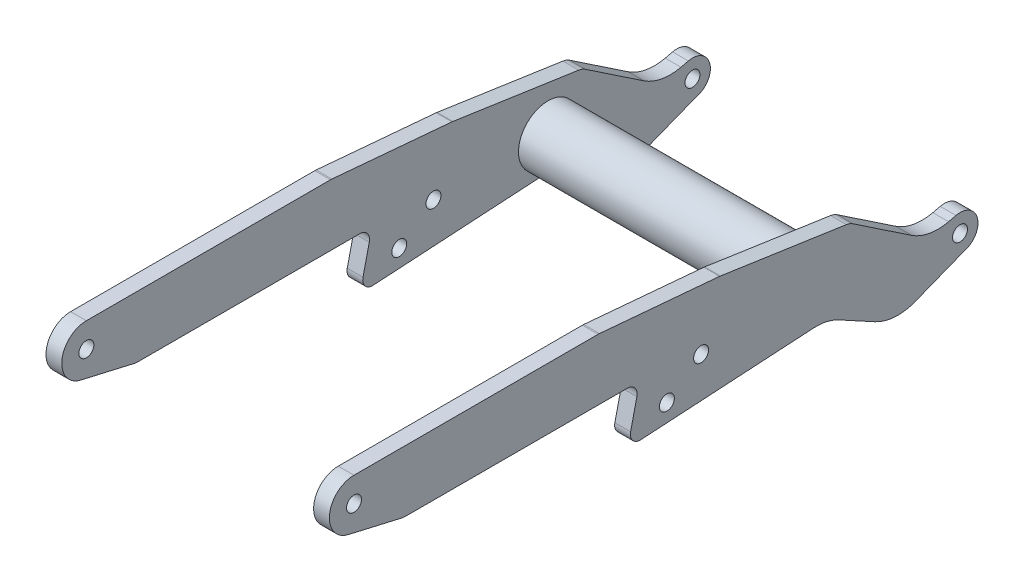
SolidWorks part; units mm, degrees
ref_plane "Front Plane" through (0, 0, 0) normal (0, 0, 1) x (1, 0, 0)
ref_plane "Top Plane" through (0, 0, 0) normal (0, 1, 0) x (1, 0, 0)
ref_plane "Right Plane" through (0, 0, 0) normal (1, 0, 0) x (0, 0, -1)
sketch "Sketch1" plane through (0, 0, 0) normal (1, 0, 0) x (0, 0, -1)
  line L0 (0, 0) -> (42.559, 0) construction
  line L1 (0, 0) -> (0, 9.8211) construction
  line L2 (42.559, 0) -> (109.2611, 0) construction
  line L3 (77, -8.75) -> (77, -3.0654) construction
  line L4 (0, 3.13) -> (31.1, 3.13)
  line L5 (31.1, 3.13) -> (46.5, 1.7827)
  line L6 (46.5, 1.7827) -> (63, -0.6391)
  line L7 (63, -0.6391) -> (70.8309, -5.8913)
  line L8 (75.5429, -6.7499) -> (76.4794, -6.5302)
  line L9 (-0.7041, -3.0498) -> (6.2959, -4.6659)
  line L12 (36.436, -11.1884) -> (41.9662, -10.8559)
  line L13 (41.9662, -10.8559) -> (58.3826, -9.8691)
  line L16 (6.2959, -4.6659) -> (34.7244, -4.6659)
  line L18 (35.9424, -6.197) -> (35.143, -9.6594)
  line L20 (66.2284, -13.1016) -> (61.6111, -10.5884)
  line L21 (77.5206, -10.9698) -> (71.29, -13.4165)
  circle A0 centre (0, 0) radius 0.95
  circle A1 centre (77, -8.75) radius 0.95
  circle A2 centre (44.1, -5.6) radius 0.95
  circle A3 centre (39.75, -8.75) radius 0.95
  arc A4 (0, 3.13) -> (-0.7041, -3.0498) centre (0, 0) ccw
  arc A6 (76.4794, -6.5302) -> (77.5206, -10.9698) centre (77, -8.75) cw
  arc A7 (58.3826, -9.8691) -> (61.6111, -10.5884) centre (58.7426, -15.8583) cw
  arc A8 (75.5429, -6.7499) -> (70.8309, -5.8913) centre (74.173, -0.9083) cw
  arc A9 (71.29, -13.4165) -> (66.2284, -13.1016) centre (69.0968, -7.8317) cw
  arc A10 (35.143, -9.6594) -> (36.436, -11.1884) centre (36.361, -9.9406) ccw
  arc A11 (34.7244, -4.6659) -> (35.9424, -6.197) centre (34.7244, -5.9159) cw
  point P29 (60.1, -9.7659)
  point P32 (73, -7.3462)
  point P39 (36.2959, -4.6659)
  dimension "D1" = 1.9
  dimension "D3" = 8.75
  dimension "D8" = 3.13
  dimension "D9" = 2.28
  dimension "D16" = 10
  dimension "D24" = 6
  dimension "D25" = 1.25
  dimension "D2" = 39.75
  dimension "D4" = 44.1
  dimension "D5" = 5.6
  dimension "D6" = 77
  dimension "D7" = 8.75
  dimension "D10" = 31.1
  dimension "D11" = 176.65
  dimension "D12" = 46.5
  dimension "D13" = 175
  dimension "D14" = 63
  dimension "D15" = 154.5
  dimension "D17" = 7
  dimension "D18" = 167
  dimension "D19" = 30
  dimension "D20" = 73.56
  dimension "D21" = 16
  dimension "D22" = 148
  dimension "D23" = 130
extrude "Boss-Extrude1" add sketch "Sketch1" along normal mid plane 36
fillet "Fillet1" radius 2 4 edges at (0, -4.6659, -6.2959) (0, -0.6391, -63) (0, 1.7827, -46.5) (0, 3.13, -31.1)
sketch "Sketch2" plane through (0, 0, 0) normal (0, 1, 0) x (1, 0, 0)
  line L0 (-18, -3.13) -> (18, -3.13) construction
  line L1 (-16, -3.13) -> (16, -3.13)
  line L2 (-16, -3.13) -> (-16, 79.28)
  line L3 (-16, 79.28) -> (16, 79.28)
  line L4 (16, -3.13) -> (16, 79.28)
  line L5 (18, 79.28) -> (-18, 79.28) construction
  line L6 (18, 70.8309) -> (18, 63.3758) construction
  line L7 (-18, 70.8309) -> (-18, 63.3758) construction
  dimension "D1" = 2
  dimension "D2" = 2
extrude "Cut-Extrude1" cut sketch "Sketch2" against normal through all both and the other way through all
sketch "Sketch3" plane through (0, 0, 0) normal (1, 0, 0) x (0, 0, -1)
  circle A0 centre (58.65, -5.75) radius 3.75
  dimension "D1" = 7.5
  dimension "D2" = 58.65
  dimension "D3" = 5.75
extrude "Boss-Extrude2" add sketch "Sketch3" along normal up to next (16 mm away) and the other way up to next (16 mm away)
